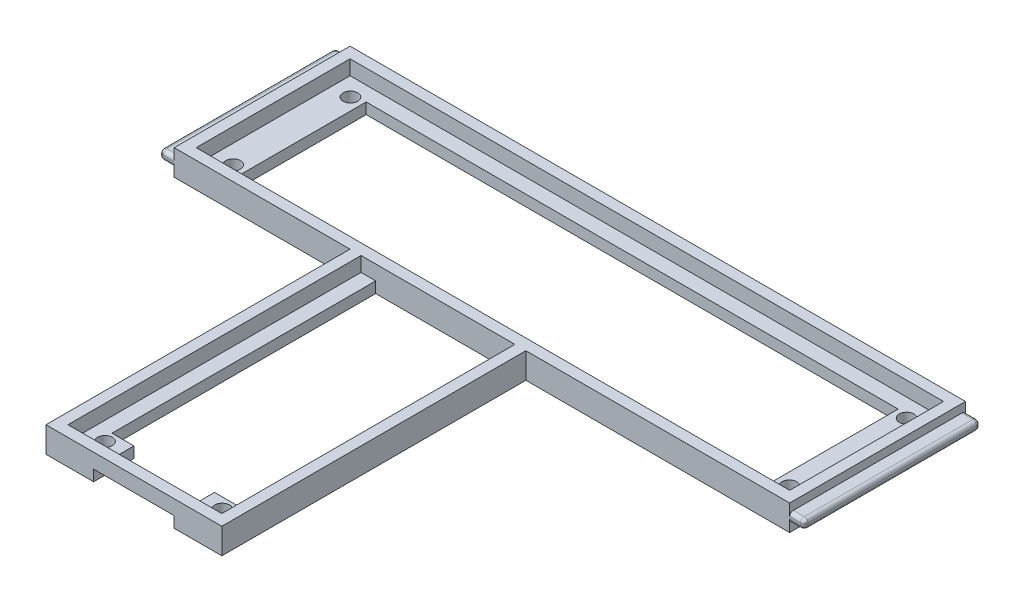
SolidWorks part; units mm, degrees
ref_plane "Front" through (0, 0, 0) normal (0, 0, 1) x (1, 0, 0)
ref_plane "Top" through (0, 0, 0) normal (0, 1, 0) x (1, 0, 0)
ref_plane "Right" through (0, 0, 0) normal (1, 0, 0) x (0, 0, -1)
sketch "Sketch2" plane through (0, 0, 0) normal (0, 1, 0) x (1, 0, 0)
  line L1 (-42, -12) -> (42, -12)
  line L2 (-42, -12) -> (-42, 12)
  line L3 (-42, 12) -> (42, 12)
  line L4 (42, -12) -> (42, 12)
  line L5 (-42, -12) -> (42, 12) construction
  line L6 (-42, 12) -> (42, -12) construction
  point P0 (0, 0)
  dimension "D1" = 84
  dimension "D2" = 24
extrude "Boss-Extrude1" add sketch "Sketch2" along normal blind 1.5
sketch "Sketch3" plane through (0, 1.5, 0) normal (0, 1, 0) x (1, 0, 0)
  line L9 (40.5, -10.5) -> (40.5, 10.5)
  line L10 (40.5, 10.5) -> (-40.5, 10.5)
  line L11 (-40.5, 10.5) -> (-40.5, -10.5)
  line L12 (-40.5, -10.5) -> (40.5, -10.5)
  line L13 (40.5, -10.5) -> (40.5, 10.5)
  line L14 (40.5, 10.5) -> (-40.5, 10.5)
  line L15 (-40.5, 10.5) -> (-40.5, -10.5)
  line L16 (-40.5, -10.5) -> (40.5, -10.5)
  line M5 (42, -12) -> (42, 12)
  line M6 (42, 12) -> (-42, 12)
  line M7 (-42, 12) -> (-42, -12)
  line M8 (-42, -12) -> (42, -12)
  dimension "D1" = 1.5
extrude "Boss-Extrude2" add sketch "Sketch3" along normal blind 2 contours L16 L15 L14 L13 M8 M5 M6 M7 region at (0, 1.5, 11.1264)
sketch "Sketch4" plane through (0, 0, 0) normal (0, -1, 0) x (1, 0, 0)
  line L1 (-37.955, -8.005) -> (37.955, -8.005) construction
  line L2 (-37.955, -8.005) -> (-37.955, 8.005) construction
  line L3 (-37.955, 8.005) -> (37.955, 8.005) construction
  line L4 (37.955, -8.005) -> (37.955, 8.005) construction
  line L5 (-37.955, -8.005) -> (37.955, 8.005) construction
  line L6 (-37.955, 8.005) -> (37.955, -8.005) construction
  circle A0 centre (-37.955, 8.005) radius 1
  circle A1 centre (37.955, 8.005) radius 1
  circle A2 centre (37.955, -8.005) radius 1
  circle A3 centre (-37.955, -8.005) radius 1
  circle A4 centre (37.955, 8.005) radius 1.045 construction
  point P0 (0, 0)
  dimension "D1" = 2
extrude "Cut-Extrude1" cut sketch "Sketch4" against normal up to next
sketch "Sketch5" plane through (0, 1.5, 0) normal (0, 1, 0) x (1, 0, 0)
  line L0 (40.5, 10.5) -> (-40.5, 10.5) construction
  line L1 (-36.3, -8.5) -> (36.3, -8.5)
  line L2 (-36.3, -8.5) -> (-36.3, 8.5)
  line L3 (-36.3, 8.5) -> (36.3, 8.5)
  line L4 (36.3, -8.5) -> (36.3, 8.5)
  line L5 (-36.3, -8.5) -> (36.3, 8.5) construction
  line L6 (-36.3, 8.5) -> (36.3, -8.5) construction
  line L7 (40.5, -10.5) -> (40.5, 10.5) construction
  point P0 (0, 0)
  dimension "D1" = 2
  dimension "D2" = 4.2
extrude "Cut-Extrude2" cut sketch "Sketch5" against normal through all
sketch "Sketch6" plane through (0, 0, 0) normal (0, -1, 0) x (1, 0, 0)
  line L24 (-36.7426, 10.105) -> (-39.1674, 10.105)
  line L25 (-39.1674, 10.105) -> (-40.3799, 8.005)
  line L26 (-40.3799, 8.005) -> (-39.1674, 5.905)
  line L27 (-39.1674, 5.905) -> (-36.7426, 5.905)
  line L28 (-36.7426, 5.905) -> (-35.5301, 8.005)
  line L29 (-35.5301, 8.005) -> (-36.7426, 10.105)
  circle A4 centre (-37.955, 8.005) radius 2.4249 construction
  dimension "D1" = 4.2
extrude "Cut-Extrude3" [suppressed] cut sketch "Sketch6" against normal blind 2
sketch "Sketch7" plane through (0, 0, 0) normal (0, -1, 0) x (1, 0, 0)
  line L0 (-42, 12) -> (-49.5, 4.5)
  line L1 (-42, -12) -> (-49.5, -4.5)
  line L2 (-49.5, 4.5) -> (-49.5, -4.5)
  line L3 (-42, 12) -> (-42, -12)
  circle A1 centre (-46.5, 0) radius 1.5
  dimension "D2" = 3
  dimension "D1" = 9
  dimension "D3" = 3
extrude "Boss-Extrude3" [suppressed] add sketch "Sketch7" against normal blind 2
sketch "Sketch8" plane through (42, 0, 0) normal (1, 0, 0) x (0, 0, -1)
  line L0 (12, 3.5) -> (12, 0) construction
  line L1 (-12, 2.375) -> (12, 2.375)
  line L2 (-12, 2.375) -> (-12, 1.125)
  line L3 (-12, 1.125) -> (12, 1.125)
  line L4 (12, 2.375) -> (12, 1.125)
  line L5 (-12, 2.375) -> (12, 1.125) construction
  line L6 (-12, 1.125) -> (12, 2.375) construction
  line L7 (-12, 3.5) -> (-12, 0) construction
  point P0 (0, 1.75)
  point P15 (12, 1.75)
  point P16 (12, 1.75)
  dimension "D1" = 1.25
extrude "Boss-Extrude4" add sketch "Sketch8" along normal blind 2
fillet "Fillet1" radius 0.5 8 edges at (44, 1.125, 0) (44, 1.75, 12) (44, 2.375, 0) (44, 1.75, -12) (43, 2.375, -12) (43, 1.125, 12) (43, 1.125, -12) (43, 2.375, 12)
mirror "Mirror1" about plane through (0, 0, 0) normal (1, 0, 0) of "Fillet1", "Boss-Extrude4"
sketch "Sketch9" plane through (0, 0, 0) normal (0, 1, 0) x (1, 0, 0)
  line L0 (-42, -12) -> (42, -12) construction
  line L1 (6, -12) -> (-18, -12)
  line L2 (6, -12) -> (6, -53.5)
  line L3 (6, -53.5) -> (-18, -53.5)
  line L4 (-18, -12) -> (-18, -53.5)
  dimension "D1" = 24
  dimension "D2" = 41.5
  dimension "D3" = 6
extrude "Boss-Extrude5" add sketch "Sketch9" along normal up to surface (1.5 mm away) up to face at (0, 1.5, 0)
sketch "Sketch10" plane through (0, 1.5, 0) normal (0, 1, 0) x (1, 0, 0)
  line L5 (-16.5, -13.5) -> (-16.5, -12)
  line L6 (-42, -12) -> (42, -12) construction
  line L7 (4.5, -13.5) -> (4.5, -12)
  line L9 (4.5, -13.5) -> (-16.5, -13.5)
  line L10 (-16.5, -13.5) -> (-16.5, -52)
  line L11 (-16.5, -52) -> (4.5, -52)
  line L12 (4.5, -52) -> (4.5, -13.5)
  line L13 (4.5, -13.5) -> (-16.5, -13.5) construction
  line L14 (-16.5, -13.5) -> (-16.5, -52)
  line L15 (-16.5, -52) -> (4.5, -52)
  line L16 (4.5, -52) -> (4.5, -13.5)
  line M7 (6, -12) -> (-18, -12)
  line M8 (-18, -12) -> (-18, -53.5)
  line M9 (-18, -53.5) -> (6, -53.5)
  line M10 (6, -53.5) -> (6, -12)
  dimension "D1" = 1.5
extrude "Boss-Extrude6" add sketch "Sketch10" along normal up to surface (2 mm away) contours L16 L15 L14 L5 L7 M7 M8 M9 M10 region at (-16.9794, 1.5, 32.75) up to face at (0, 3.5, 0)
sketch "Sketch11" plane through (0, 1.5, 0) normal (0, 1, 0) x (1, 0, 0)
  line L0 (-16.5, -52) -> (4.5, -52) construction
  line L1 (-16.5, -12) -> (-16.5, -52) construction
  line L2 (-14, -49.45) -> (2, -49.45) construction
  circle A0 centre (-14, -49.45) radius 1
  circle A1 centre (2, -49.45) radius 1
  point P8 (-6, -52)
  point P9 (-6, -49.45)
  dimension "D1" = 2
  dimension "D2" = 2.55
  dimension "D3" = 2.5
extrude "Cut-Extrude4" cut sketch "Sketch11" against normal through all
sketch "Sketch12" plane through (0, 1.5, 0) normal (0, 1, 0) x (1, 0, 0)
  line L0 (-16.5, -52) -> (4.5, -52) construction
  line L1 (-14.5, -48) -> (2.5, -48)
  line L2 (-14.5, -48) -> (-14.5, -12)
  line L3 (-14.5, -12) -> (2.5, -12)
  line L4 (2.5, -48) -> (2.5, -12)
  line L5 (-16.5, -12) -> (-16.5, -52) construction
  line L6 (4.5, -52) -> (4.5, -12) construction
  line L7 (-16.5, -12) -> (4.5, -12) construction
  dimension "D1" = 4
  dimension "D2" = 2
  dimension "D3" = 2
extrude "Cut-Extrude5" cut sketch "Sketch12" against normal through all
sketch "Sketch13" plane through (0, 0, 0) normal (0, -1, 0) x (1, 0, 0)
  line L0 (-14.5, 48) -> (2.5, 48) construction
  line L1 (-11.5, 48) -> (-0.5, 48)
  line L2 (-11.5, 48) -> (-11.5, 53.5)
  line L3 (-11.5, 53.5) -> (-0.5, 53.5)
  line L4 (-0.5, 48) -> (-0.5, 53.5)
  line L5 (-18, 53.5) -> (6, 53.5) construction
  line L6 (2.5, 12) -> (-14.5, 12) construction
  point P8 (-6, 48)
  point P11 (-6, 12)
  dimension "D1" = 11
extrude "Cut-Extrude6" cut sketch "Sketch13" against normal up to surface (1.5 mm away) up to face at (-14, 1.5, 50.45)
